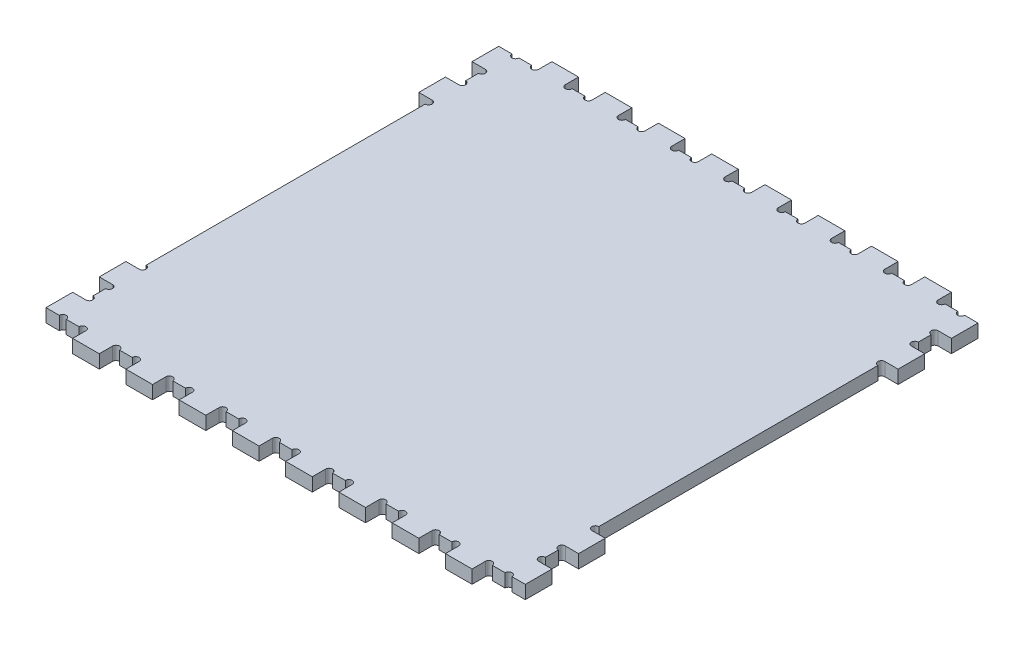
SolidWorks part; units mm, degrees
ref_plane "Front Plane" through (0, 0, 0) normal (0, 0, 1) x (1, 0, 0)
ref_plane "Top Plane" through (0, 0, 0) normal (0, 1, 0) x (1, 0, 0)
ref_plane "Right Plane" through (0, 0, 0) normal (1, 0, 0) x (0, 0, -1)
sketch "Sketch1" plane through (0, 0, 0) normal (0, 1, 0) x (1, 0, 0)
  line L1 (228.6, -228.6) -> (-228.6, -228.6)
  line L2 (228.6, -228.6) -> (228.6, 228.6)
  line L3 (228.6, 228.6) -> (-228.6, 228.6)
  line L4 (-228.6, -228.6) -> (-228.6, 228.6)
  line L5 (228.6, -228.6) -> (-228.6, 228.6) construction
  line L6 (228.6, 228.6) -> (-228.6, -228.6) construction
  point P0 (0, 0)
  dimension "D1" = 457.2
  dimension "D2" = 457.2
extrude "Boss-Extrude1" add sketch "Sketch1" along normal blind 12.7
sketch "Sketch2" plane through (0, 12.7, 0) normal (0, 1, 0) x (1, 0, 0)
  line L0 (228.6, 228.6) -> (-228.6, 228.6) construction
  line L1 (-215.9, 228.6) -> (-190.5, 228.6)
  line L2 (-215.9, 228.6) -> (-215.9, 215.9)
  line L3 (-215.9, 215.9) -> (-190.5, 215.9)
  line L4 (-190.5, 228.6) -> (-190.5, 215.9)
  line L5 (-215.9, 215.9) -> (-228.6, 215.9) construction
  line L6 (-228.6, 228.6) -> (-228.6, -228.6) construction
  circle A0 centre (-212.598, 215.9) radius 3.302
  circle A1 centre (-193.802, 215.9) radius 3.302
  line M8 (228.6, 228.6) -> (-228.6, 228.6)
  dimension "D3" = 6.604
  dimension "D4" = 6.604
  dimension "D1" = 25.4
  dimension "D2" = 12.7
  dimension "D5" = 12.7
extrude "Cut-Extrude1" cut sketch "Sketch2" against normal blind 12.7 contours A1 L4 L2 A0 L3 M8 | L3 A0 | L3 A1 | L3 A1 | L3 A0 region at (-203.2, 12.7, -222.8379) region at (-212.598, 12.7, -217.3014) region at (-212.598, 12.7, -214.4986) region at (-193.802, 12.7, -214.4986) region at (-193.802, 12.7, -217.3014)
pattern_linear "LPattern1" count 9 spacing 50.8 along (1, 0, 0) of "Cut-Extrude1"
ref_plane "Plane1" through (0, 0, 0) normal (0, 0, -1) x (-1, 0, 0)
ref_plane "Plane2" through (0, 0, 0) normal (-1, 0, 0) x (0, 0, 1)
mirror "Mirror1" about plane through (0, 0, 0) normal (0, 0, -1) of "LPattern1"
sketch "Sketch3" plane through (0, 12.7, 0) normal (0, 1, 0) x (1, 0, 0)
  line L1 (-228.6, 228.6) -> (-215.9, 228.6)
  line L2 (-228.6, 228.6) -> (-228.6, 215.9)
  line L3 (-228.6, 215.9) -> (-215.9, 215.9)
  line L4 (-215.9, 228.6) -> (-215.9, 215.9)
extrude "Cut-Extrude2" cut sketch "Sketch3" against normal through all
mirror "Mirror2" about plane through (0, 0, 0) normal (-1, 0, 0) of "Cut-Extrude2"
mirror "Mirror3" about plane through (0, 0, 0) normal (0, 0, -1) of "Mirror2"
sketch "Sketch4" plane through (0, 12.7, 0) normal (0, 1, 0) x (1, 0, 0)
  line L0 (-228.6, 215.9) -> (-228.6, -215.9) construction
  line L1 (-228.6, 190.5) -> (-215.9, 190.5)
  line L2 (-228.6, 190.5) -> (-228.6, 165.1)
  line L3 (-228.6, 165.1) -> (-215.9, 165.1)
  line L4 (-215.9, 190.5) -> (-215.9, 165.1)
  line L5 (-215.9, 190.5) -> (-186.3664, 190.5) construction
  line L6 (-186.3664, 190.5) -> (-186.3664, 228.6) construction
  line L7 (-165.1, 228.6) -> (-190.5, 228.6) construction
  circle A0 centre (-215.9, 187.198) radius 3.302
  circle A1 centre (-215.9, 168.402) radius 3.302
  dimension "D3" = 6.604
  dimension "D4" = 6.604
  dimension "D1" = 12.7
  dimension "D2" = 25.4
  dimension "D5" = 38.1
extrude "Cut-Extrude3" cut sketch "Sketch4" against normal through all contours A1 L4 A0 L1 L2 L3 | L4 A0 | L4 A1 | L4 A1 | L4 A0 region at (-222.8379, 12.7, -177.8) region at (-214.4986, 12.7, -187.198) region at (-217.3014, 12.7, -187.198) region at (-217.3014, 12.7, -168.402) region at (-214.4986, 12.7, -168.402)
pattern_linear "LPattern2" count 9 spacing 50.8 along (0, 0, 1) of "Cut-Extrude3"
mirror "Mirror4" about plane through (0, 0, 0) normal (-1, 0, 0) of "LPattern2"
sketch "Sketch5" plane through (0, 12.7, 0) normal (0, 1, 0) x (1, 0, 0)
  line L0 (-165.1, 114.3) -> (-165.1, 215.9) construction
  line L1 (-158.496, 114.3) -> (-146.304, 114.3)
  line L2 (-165.1, 114.3) -> (-165.1, 101.6)
  line L3 (-158.496, 101.6) -> (-146.304, 101.6)
  line L4 (-139.7, 114.3) -> (-139.7, 101.6)
  arc A0 (-158.496, 114.3) -> (-165.1, 114.3) centre (-161.798, 114.3) ccw
  arc A1 (-139.7, 114.3) -> (-146.304, 114.3) centre (-143.002, 114.3) ccw
  arc A2 (-146.304, 101.6) -> (-139.7, 101.6) centre (-143.002, 101.6) ccw
  arc A3 (-165.1, 101.6) -> (-158.496, 101.6) centre (-161.798, 101.6) ccw
  dimension "D3" = 6.604
  dimension "D1" = 25.4
  dimension "D2" = 12.7
  dimension "D4" = 101.6
extrude "Cut-Extrude4" cut sketch "Sketch5" against normal through all
pattern_linear "LPattern3" count 7 spacing 50.8 along (1, 0, 0) of "Cut-Extrude4"
sketch "Sketch6" plane through (0, 12.7, 0) normal (0, 1, 0) x (1, 0, 0)
  line L1 (-228.6, 139.7) -> (-215.9, 139.7)
  line L2 (-228.6, 139.7) -> (-228.6, -139.7)
  line L3 (-228.6, -139.7) -> (-215.9, -139.7)
  line L4 (-215.9, 139.7) -> (-215.9, -139.7)
  line L5 (228.6, 139.7) -> (215.9, 139.7)
  line L6 (228.6, 139.7) -> (228.6, -139.7)
  line L7 (228.6, -139.7) -> (215.9, -139.7)
  line L8 (215.9, 139.7) -> (215.9, -139.7)
extrude "Cut-Extrude5" cut sketch "Sketch6" against normal through all
sketch "Sketch7" plane through (0, 12.7, 0) normal (0, 1, 0) x (1, 0, 0)
  line L0 (-215.9, 133.096) -> (-215.9, 120.904) construction
  line L1 (-215.9, 133.096) -> (-208.346, 133.096)
  line L2 (-215.9, 133.096) -> (-215.9, -130.6902)
  line L3 (-215.9, -130.6902) -> (-208.346, -130.6902)
  line L4 (-208.346, 133.096) -> (-208.346, -130.6902)
  line L5 (215.9, 133.096) -> (215.9, 120.904) construction
  line L6 (215.9, 133.096) -> (210.1226, 133.096)
  line L7 (215.9, 133.096) -> (215.9, -128.0701)
  line L8 (215.9, -128.0701) -> (210.1226, -128.0701)
  line L9 (210.1226, 133.096) -> (210.1226, -128.0701)
  arc A0 (-215.9, 133.096) -> (-215.9, 139.7) centre (-215.9, 136.398) ccw construction
extrude "Boss-Extrude2" add sketch "Sketch7" against normal blind 12.7
sketch "Sketch8" plane through (0, 12.7, 0) normal (0, 1, 0) x (1, 0, 0)
  line L1 (-193.1987, 143.9727) -> (177.8487, 143.9727)
  line L2 (-193.1987, 143.9727) -> (-193.1987, 79.926)
  line L3 (-193.1987, 79.926) -> (177.8487, 79.926)
  line L4 (177.8487, 143.9727) -> (177.8487, 79.926)
extrude "Boss-Extrude3" add sketch "Sketch8" against normal up to surface (12.7 mm away) up to face at (0, 0, 0)
